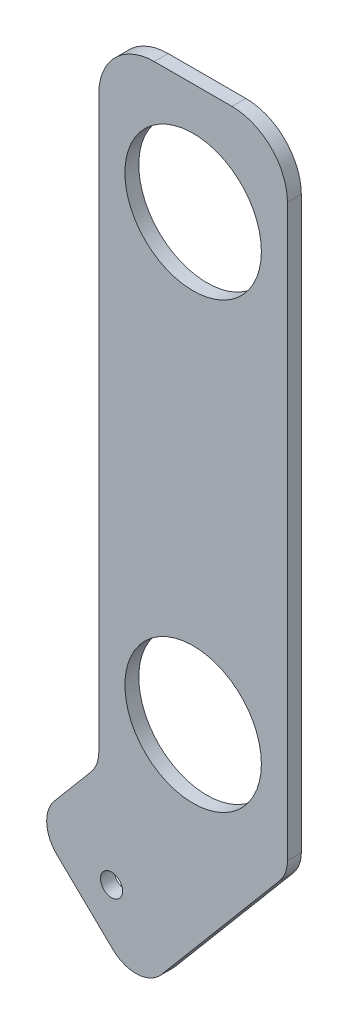
SolidWorks part; units mm, degrees
material "6061 Alloy"
ref_plane "Front Plane" through (0, 0, 0) normal (0, 0, 1) x (1, 0, 0)
ref_plane "Top Plane" through (0, 0, 0) normal (0, 1, 0) x (1, 0, 0)
ref_plane "Right Plane" through (0, 0, 0) normal (1, 0, 0) x (0, 0, -1)
sketch "Sketch1" plane through (0, 0, 0) normal (0, 0, 1) x (1, 0, 0)
  line L0 (0, 0) -> (0, -101.6) construction
  line L1 (21.59, -120.5575) -> (-21.59, -120.5575) construction
  line L2 (-8.89, 25.4) -> (8.89, 25.4)
  line L3 (-21.59, 12.7) -> (-21.59, -117.7751)
  line L5 (21.59, 12.7) -> (21.59, -117.7751)
  line L9 (-23.3829, -122.6853) -> (-31.7351, -132.597)
  line L10 (-36.322, 25.4) -> (20.828, 25.4) construction
  line L11 (-36.322, 25.4) -> (-36.322, -203.2) construction
  line L12 (-36.322, -203.2) -> (20.828, -203.2) construction
  line L13 (20.828, 25.4) -> (20.828, -203.2) construction
  line L14 (-31.203, -142.9869) -> (-18.3873, -155.3705)
  line L15 (-7.2652, -154.801) -> (19.7971, -122.6853)
  circle A0 centre (0, 0) radius 38.1 construction
  circle A1 centre (0, -101.6) radius 38.1 construction
  circle A2 centre (0, 0) radius 15.621
  circle A3 centre (0, -101.6) radius 15.621
  arc A6 (8.89, 25.4) -> (21.59, 12.7) centre (8.89, 12.7) cw
  arc A7 (-8.89, 25.4) -> (-21.59, 12.7) centre (-8.89, 12.7) ccw
  circle A10 centre (-18.6799, -142.7255) radius 2.54
  arc A11 (-31.7351, -132.597) -> (-31.203, -142.9869) centre (-25.908, -137.5071) ccw
  arc A12 (-18.3873, -155.3705) -> (-7.2652, -154.801) centre (-13.0923, -149.8908) ccw
  arc A13 (-23.3829, -122.6853) -> (-21.59, -117.7751) centre (-29.21, -117.7751) ccw
  arc A14 (19.7971, -122.6853) -> (21.59, -117.7751) centre (13.97, -117.7751) ccw
  point P13 (-192.705, 39.2708)
  point P20 (21.59, 25.4)
  point P23 (-21.59, 25.4)
  point P31 (-36.322, -138.0404)
  dimension "D2" = 76.2
  dimension "D3" = 76.2
  dimension "D4" = 31.242
  dimension "D5" = 31.242
  dimension "D10" = 228.6
  dimension "D11" = 36.322
  dimension "D13" = 5.08
  dimension "D19" = 7.62
  dimension "D20" = 7.62
  dimension "D21" = 12.7
  dimension "D1" = 101.6
  dimension "D6" = 43.18
  dimension "D7" = 21.59
  dimension "D8" = 25.4
  dimension "D9" = 57.15
  dimension "D12" = 25.4
  dimension "D14" = 33.02
  dimension "D15" = 16.51
  dimension "D16" = 8.89
  dimension "D17" = 44.018
  dimension "D18" = 18.9575
extrude "Boss-Extrude1" add sketch "Sketch1" along normal blind 3.175
